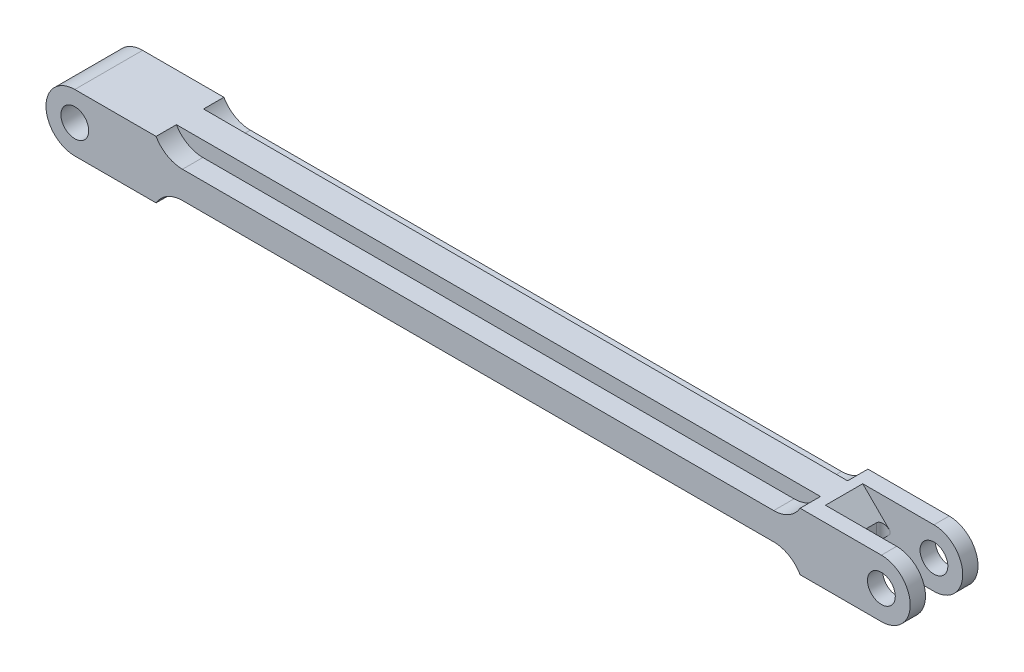
SolidWorks part; units mm, degrees
ref_plane "Plano frontal" through (0, 0, 0) normal (0, 0, 1) x (1, 0, 0)
ref_plane "Plano superior" through (0, 0, 0) normal (0, 1, 0) x (1, 0, 0)
ref_plane "Plano direito" through (0, 0, 0) normal (1, 0, 0) x (0, 0, -1)
sketch "Esboço1" plane through (0, 0, 0) normal (0, 0, 1) x (1, 0, 0)
  line L0 (-29.0717, 188.3739) -> (208.8814, 188.3739)
  line L1 (-29.0717, 171.3739) -> (208.8814, 171.3739)
  circle A0 centre (-29.0717, 179.8739) radius 4.1
  circle A1 centre (208.8814, 179.8739) radius 4.1
  arc A2 (-29.0717, 188.3739) -> (-29.0717, 171.3739) centre (-29.0717, 179.8739) ccw
  arc A3 (208.8814, 171.3739) -> (208.8814, 188.3739) centre (208.8814, 179.8739) ccw
  dimension "D1" = 8.2
  dimension "D2" = 237.9531
  dimension "D3" = 8.5
extrude "Ressalto-extrusão1" add sketch "Esboço1" along normal mid plane 20
sketch "Esboço2" plane through (0, 188.3739, 0) normal (0, 1, 0) x (1, 0, 0)
  line L0 (217.3814, -10) -> (217.3814, 10) construction
  line L1 (217.3814, 5.5) -> (193.8814, 5.5)
  line L2 (217.3814, 5.5) -> (217.3814, -5.5)
  line L3 (217.3814, -5.5) -> (193.8814, -5.5)
  line L4 (193.8814, 5.5) -> (193.8814, -5.5)
  line L5 (200.8814, -5) -> (216.8814, -5) construction
  line L6 (216.8814, 5) -> (200.8814, 5) construction
  line L7 (198.8814, -5) -> (198.8814, 5) construction
  dimension "D1" = 0.5
  dimension "D2" = 0.5
  dimension "D3" = 5
extrude "Corte-extrusão1" cut sketch "Esboço2" against normal through all
fillet "Filete1" radius 2 2 edges at (193.8814, 179.8739, 5.5) (193.8814, 179.8739, -5.5)
sketch "Esboço4" plane through (0, 0, 10) normal (0, 0, 1) x (1, 0, 0)
  line L0 (208.8814, 188.3739) -> (-29.0717, 188.3739) construction
  line L1 (184.9048, 154.5152) -> (-5.0952, 154.5152)
  line L2 (184.9048, 154.5152) -> (184.9048, 191.1372)
  line L3 (184.9048, 191.1372) -> (-5.0952, 191.1372)
  line L4 (-5.0952, 154.5152) -> (-5.0952, 191.1372)
  line L5 (184.9048, 154.5152) -> (-5.0952, 191.1372) construction
  line L6 (184.9048, 191.1372) -> (-5.0952, 154.5152) construction
  point P0 (89.9048, 172.8262)
  point P8 (89.9048, 188.3739)
  dimension "D1" = 190
extrude "Corte-extrusão3" cut sketch "Esboço4" against normal through all
sketch "Esboço5" plane through (-5.0952, 0, 0) normal (1, 0, 0) x (0, 0, -1)
  line L0 (-10, 188.3739) -> (10, 188.3739) construction
  line L1 (4, 171.3739) -> (-4, 171.3739)
  line L2 (4, 171.3739) -> (4, 175.8739)
  line L3 (4, 188.3739) -> (-4, 188.3739)
  line L4 (-4, 171.3739) -> (-4, 175.8739)
  line L5 (4, 171.3739) -> (-4, 188.3739) construction
  line L6 (4, 188.3739) -> (-4, 171.3739) construction
  line L7 (-10, 188.3739) -> (-10, 171.3739) construction
  line L8 (10, 188.3739) -> (10, 171.3739) construction
  line L9 (-10, 175.8739) -> (-4, 175.8739)
  line L10 (-10, 175.8739) -> (-10, 183.8739)
  line L11 (-10, 183.8739) -> (-4, 183.8739)
  line L12 (10, 175.8739) -> (10, 183.8739)
  line L13 (-10, 175.8739) -> (10, 183.8739) construction
  line L14 (-10, 183.8739) -> (10, 175.8739) construction
  line L15 (4, 183.8739) -> (10, 183.8739)
  line L16 (-4, 183.8739) -> (-4, 188.3739)
  line L17 (4, 175.8739) -> (10, 175.8739)
  line L18 (4, 183.8739) -> (4, 188.3739)
  point P0 (0, 179.8739)
  point P9 (-10, 179.8739)
  point P10 (0, 188.3739)
  point P11 (0, 179.8739)
  dimension "D1" = 8
  dimension "D2" = 8
extrude "Ressalto-extrusão2" add sketch "Esboço5" along normal up to surface (190 mm away) up to face at (184.9048, 179.8739, 0)
fillet "Filete3" radius 9 8 edges at (-5.0952, 183.8739, 7) (184.9048, 175.8739, 7) (184.9048, 175.8739, -7) (184.9048, 183.8739, 7) (184.9048, 183.8739, -7) (-5.0952, 175.8739, -7) (-5.0952, 183.8739, -7) (-5.0952, 175.8739, 7)
sketch "Esboço6" plane through (0, 0, 0) normal (0, 0, 1) x (1, 0, 0)
  line L0 (208.8814, 179.8739) -> (196.3814, 179.8739)
  line L1 (187.8814, 188.3739) -> (196.3814, 179.8739)
  line L3 (208.8814, 188.3739) -> (184.9048, 188.3739) construction
  line L4 (193.8814, 188.3739) -> (193.8814, 171.3739) construction
  line L5 (208.8814, 179.8739) -> (208.8814, 194.3004)
  line L6 (208.8814, 194.3004) -> (187.8814, 194.3004)
  line L7 (187.8814, 194.3004) -> (187.8814, 188.3739)
  dimension "D1" = 6
  dimension "D2" = 45
extrude "Corte-extrusão4" cut sketch "Esboço6" against normal mid plane 11
ref_plane "Plano1" through (0, 179.8739, 0) normal (0, 1, 0) x (1, 0, 0)
mirror "Espelhar1" about plane through (0, 179.8739, 0) normal (0, 1, 0) of "Corte-extrusão4"
